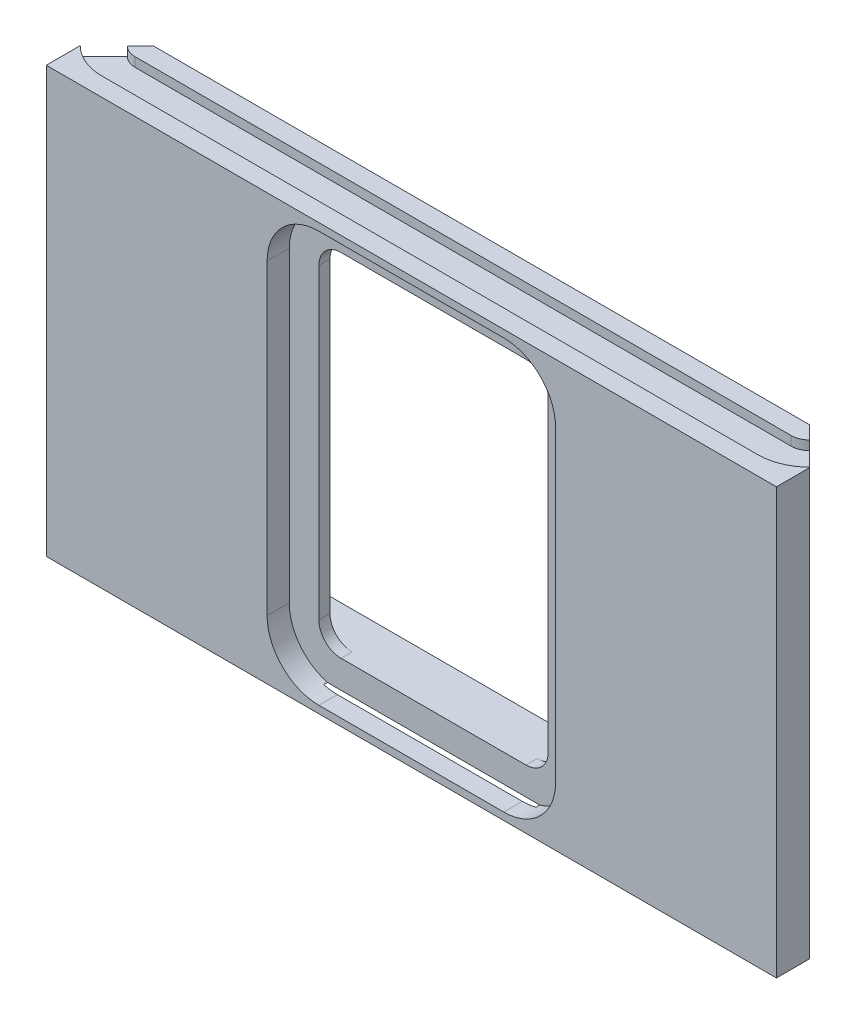
SolidWorks part; units mm, degrees
ref_plane "Front Plane" through (0, 0, 0) normal (0, 0, 1) x (1, 0, 0)
ref_plane "Top Plane" through (0, 0, 0) normal (0, 1, 0) x (1, 0, 0)
ref_plane "Right Plane" through (0, 0, 0) normal (1, 0, 0) x (0, 0, -1)
sketch "Sketch1" plane through (0, 0, 0) normal (0, 0, 1) x (1, 0, 0)
  line L2 (-98.7, -57.5) -> (-98.7, 57.5)
  line L5 (-98.7, 57.5) -> (98.7, 57.5)
  line L9 (98.7, 57.5) -> (98.7, -57.5)
  line L14 (98.7, -57.5) -> (-98.7, -57.5)
  dimension "D1" = 115
  dimension "D2" = 57.5
extrude "Boss-Extrude1" add sketch "Sketch1" along normal blind 9
sketch "Sketch2" plane through (0, 57.5, 0) normal (0, 1, 0) x (1, 0, 0)
  line L0 (-88.7, 10) -> (88.7, 10)
  line L1 (98.7, 0) -> (-98.7, 0) construction
  line L2 (-98.7, 0) -> (-88.7, 10)
  line L3 (98.7, 0) -> (88.7, 10)
  line L5 (-98.7, 0) -> (98.7, 0)
  dimension "D1" = 10
extrude "Boss-Extrude2" add sketch "Sketch2" against normal blind 10
sketch "Sketch3" plane through (0, 0, 9) normal (0, 0, 1) x (1, 0, 0)
  line L5 (-98.7, -57.5) -> (98.7, -57.5) construction
  line L6 (-25, 47.5) -> (25, 47.5)
  line L7 (-31, 41.5) -> (-31, -41.5)
  line L8 (-25, -47.5) -> (25, -47.5)
  line L9 (31, 41.5) -> (31, -41.5)
  arc A4 (25, -47.5) -> (31, -41.5) centre (25, -41.5) ccw
  arc A5 (25, 47.5) -> (31, 41.5) centre (25, 41.5) cw
  arc A6 (-31, -41.5) -> (-25, -47.5) centre (-25, -41.5) ccw
  arc A7 (-25, 47.5) -> (-31, 41.5) centre (-25, 41.5) ccw
  dimension "D2" = 10
  dimension "D5" = 6
  dimension "D3" = 50
extrude "Cut-Extrude1" cut sketch "Sketch3" against normal up to surface (9 mm away) up to face at (0, -5, 0)
sketch "Sketch4" plane through (0, 0, 9) normal (0, 0, 1) x (1, 0, 0)
  line L4 (-25, -55.5) -> (25, -55.5)
  line L5 (-25, -55.5) -> (25, -55.5)
  line L6 (39, -41.5) -> (39, 41.5)
  line L7 (39, -41.5) -> (39, 41.5)
  line L8 (25, 55.5) -> (-25, 55.5)
  line L9 (25, 55.5) -> (-25, 55.5)
  line L10 (-39, 41.5) -> (-39, -41.5)
  line L11 (-39, 41.5) -> (-39, -41.5)
  arc A4 (25, -55.5) -> (39, -41.5) centre (25, -41.5) ccw
  arc A5 (25, -55.5) -> (39, -41.5) centre (25, -41.5) ccw
  arc A6 (39, 41.5) -> (25, 55.5) centre (25, 41.5) ccw
  arc A7 (39, 41.5) -> (25, 55.5) centre (25, 41.5) ccw
  arc A8 (-25, 55.5) -> (-39, 41.5) centre (-25, 41.5) ccw
  arc A9 (-25, 55.5) -> (-39, 41.5) centre (-25, 41.5) ccw
  arc A10 (-39, -41.5) -> (-25, -55.5) centre (-25, -41.5) ccw
  arc A11 (-39, -41.5) -> (-25, -55.5) centre (-25, -41.5) ccw
  dimension "D1" = 8
extrude "Cut-Extrude2" cut sketch "Sketch4" against normal blind 6
sketch "Sketch5" plane through (0, 57.5, 0) normal (0, 1, 0) x (1, 0, 0)
  line L0 (-88.7, 5) -> (88.7, 5)
  line L1 (-88.7, 10) -> (-98.7, 0) construction
  line L2 (98.7, 0) -> (88.7, 10) construction
  line L3 (88.7, 10) -> (-88.7, 10) construction
  line L4 (-88.7, -4) -> (88.7, -4)
  line L11 (-98.5995, 0.1005) -> (-92.2355, 6.4645)
  line L12 (92.2355, 6.4645) -> (98.5995, 0.1005)
  arc A0 (-88.7, 5) -> (-92.2355, 6.4645) centre (-88.7, 10) cw
  arc A1 (88.7, 5) -> (92.2355, 6.4645) centre (88.7, 10) ccw
  arc A2 (88.7, -4) -> (98.5995, 0.1005) centre (88.7, 10) ccw
  arc A3 (-88.7, -4) -> (-98.5995, 0.1005) centre (-88.7, 10) cw
  dimension "D1" = 5
  dimension "D2" = 9
extrude "Cut-Extrude3" cut sketch "Sketch5" against normal blind 2.5
mirror "Mirror2" about plane through (0, 0, 0) normal (0, 1, 0) of "Cut-Extrude3", "Boss-Extrude2"
